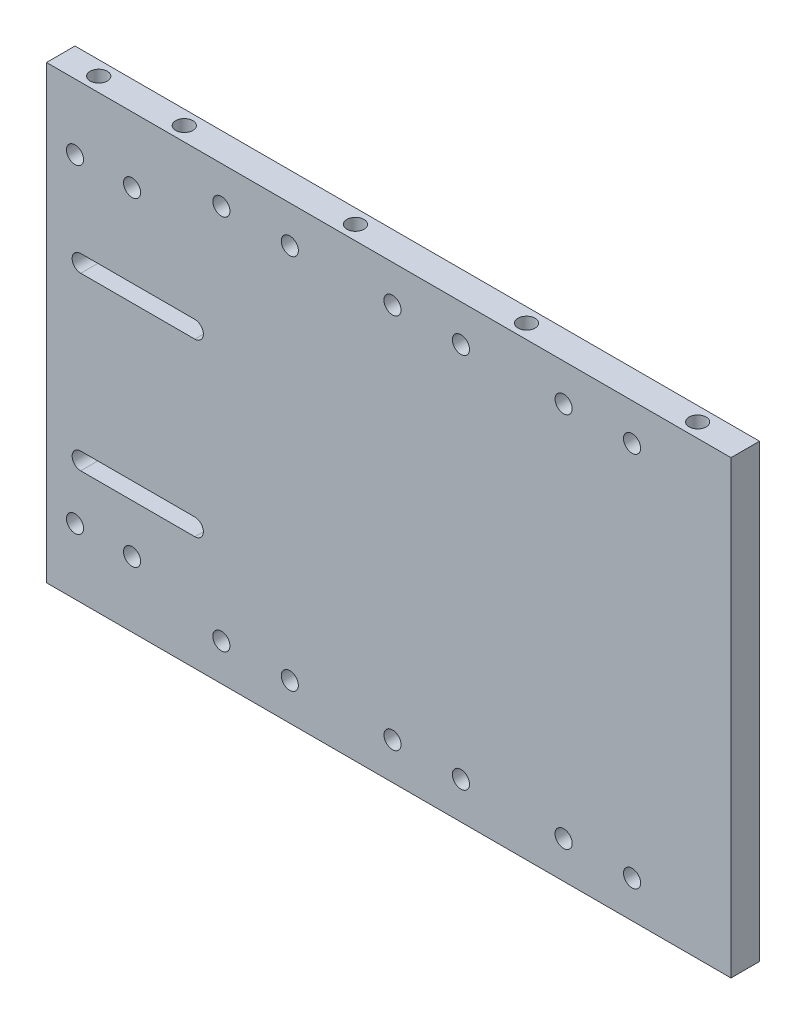
SolidWorks part; units mm, degrees
ref_plane "前视基准面" through (0, 0, 0) normal (0, 0, 1) x (1, 0, 0)
ref_plane "上视基准面" through (0, 0, 0) normal (0, 1, 0) x (1, 0, 0)
ref_plane "右视基准面" through (0, 0, 0) normal (1, 0, 0) x (0, 0, -1)
other "Configuration Table"
sketch "草图1" plane through (0, 0, 0) normal (0, 0, 1) x (1, 0, 0)
  line L1 (-60, -39.5) -> (60, -39.5)
  line L2 (-60, -39.5) -> (-60, 39.5)
  line L3 (-60, 39.5) -> (60, 39.5)
  line L4 (60, -39.5) -> (60, 39.5)
  line L5 (-60, -39.5) -> (60, 39.5) construction
  line L6 (-60, 39.5) -> (60, -39.5) construction
  point P0 (0, 0)
  dimension "D1" = 79
  dimension "D2" = 120
extrude "凸台-拉伸1" add sketch "草图1" along normal blind 5
sketch "草图2" plane through (0, 0, 0) normal (0, 0, -1) x (-1, 0, 0)
  circle A0 centre (-42.656, -33) radius 3.1
  circle A1 centre (-30.656, -33) radius 3.1
extrude "切除-拉伸1" cut sketch "草图2" against normal blind 1.5
sketch "草图3" plane through (0, 0, 1.5) normal (0, 0, -1) x (-1, 0, 0)
  circle A0 centre (-42.656, -33) radius 1.5
  circle A1 centre (-30.656, -33) radius 1.5
extrude "切除-拉伸2" cut sketch "草图3" against normal through all
pattern_linear "阵列(线性)1" count 3 spacing 30 along (-1, 0, 0) of "切除-拉伸1", "切除-拉伸2"
mirror "镜向2" about plane through (0, 0, 0) normal (0, 1, 0) of "阵列(线性)1"
sketch "草图4" plane through (0, 0, 0) normal (0, 0, -1) x (-1, 0, 0)
  line L0 (34, 12) -> (54, 12) construction
  line L1 (34, 15.1) -> (54, 15.1)
  line L2 (34, 8.9) -> (54, 8.9)
  line L3 (60, 39.5) -> (60, -39.5) construction
  line L4 (34.3421, -3) -> (54.815, -3) construction
  line L5 (34.3421, 17) -> (34.3421, -23) construction
  line L6 (54.815, 17) -> (54.815, -6) construction
  line L7 (34, -18) -> (54, -18) construction
  line L8 (34, -21.1) -> (54, -21.1)
  line L9 (34, -14.9) -> (54, -14.9)
  arc A4 (34, 15.1) -> (34, 8.9) centre (34, 12) ccw
  arc A5 (54, 8.9) -> (54, 15.1) centre (54, 12) ccw
  arc A6 (34, -21.1) -> (34, -14.9) centre (34, -18) cw
  arc A7 (54, -14.9) -> (54, -21.1) centre (54, -18) cw
  point P8 (44, 12)
  point P17 (44, -18)
  dimension "D1" = 20
  dimension "D2" = 6
extrude "切除-拉伸3" cut sketch "草图4" against normal blind 1.5
sketch "草图5" plane through (0, 0, 1.5) normal (0, 0, -1) x (-1, 0, 0)
  line L0 (54, 12) -> (34, 12) construction
  line L1 (54, 10.5) -> (34, 10.5)
  line L2 (54, 13.5) -> (34, 13.5)
  line L3 (60, 39.5) -> (60, -39.5) construction
  line L4 (34.3421, -3) -> (54.815, -3) construction
  line L5 (54.815, 17) -> (54.815, -6) construction
  line L6 (54, -18) -> (34, -18) construction
  line L7 (54, -16.5) -> (34, -16.5)
  line L8 (54, -19.5) -> (34, -19.5)
  arc A0 (54, 10.5) -> (54, 13.5) centre (54, 12) ccw
  arc A1 (34, 13.5) -> (34, 10.5) centre (34, 12) ccw
  arc A2 (54, -16.5) -> (54, -19.5) centre (54, -18) cw
  arc A3 (34, -19.5) -> (34, -16.5) centre (34, -18) cw
  point P4 (44, 12)
  point P18 (44, -18)
  dimension "D1" = 20
  dimension "D2" = 6
extrude "切除-拉伸4" cut sketch "草图5" against normal through all
sketch "草图6" plane through (0, 0, 5) normal (0, 0, 1) x (1, 0, 0)
  circle A0 centre (-45, 28) radius 1.5 construction
  circle A1 centre (-45, 28) radius 1.5
  circle A2 centre (-55, 28) radius 1.5 construction
  circle A3 centre (-55, 28) radius 1.5
  circle A4 centre (-55, -28) radius 1.5 construction
  circle A5 centre (-55, -28) radius 1.5
  circle A6 centre (-45, -28) radius 1.5 construction
  circle A7 centre (-45, -28) radius 1.5
extrude "切除-拉伸5" cut sketch "草图6" against normal through all
sketch "草图7" plane through (0, -39.5, 0) normal (0, -1, 0) x (1, 0, 0)
  line L0 (46.656, 31) -> (46.656, 5) construction
  circle A0 centre (51.656, 2.5) radius 1.5
  circle A1 centre (21.656, 2.5) radius 1.5
  circle A2 centre (-8.344, 2.5) radius 1.5
  circle A3 centre (-38.344, 2.5) radius 1.5
  circle A4 centre (-53.344, 2.5) radius 1.5
  dimension "D1" = 5
  dimension "D2" = 15
extrude "切除-拉伸6" cut sketch "草图7" against normal blind 5
mirror "镜向3" about plane through (0, 0, 0) normal (0, 1, 0) of "切除-拉伸6"
